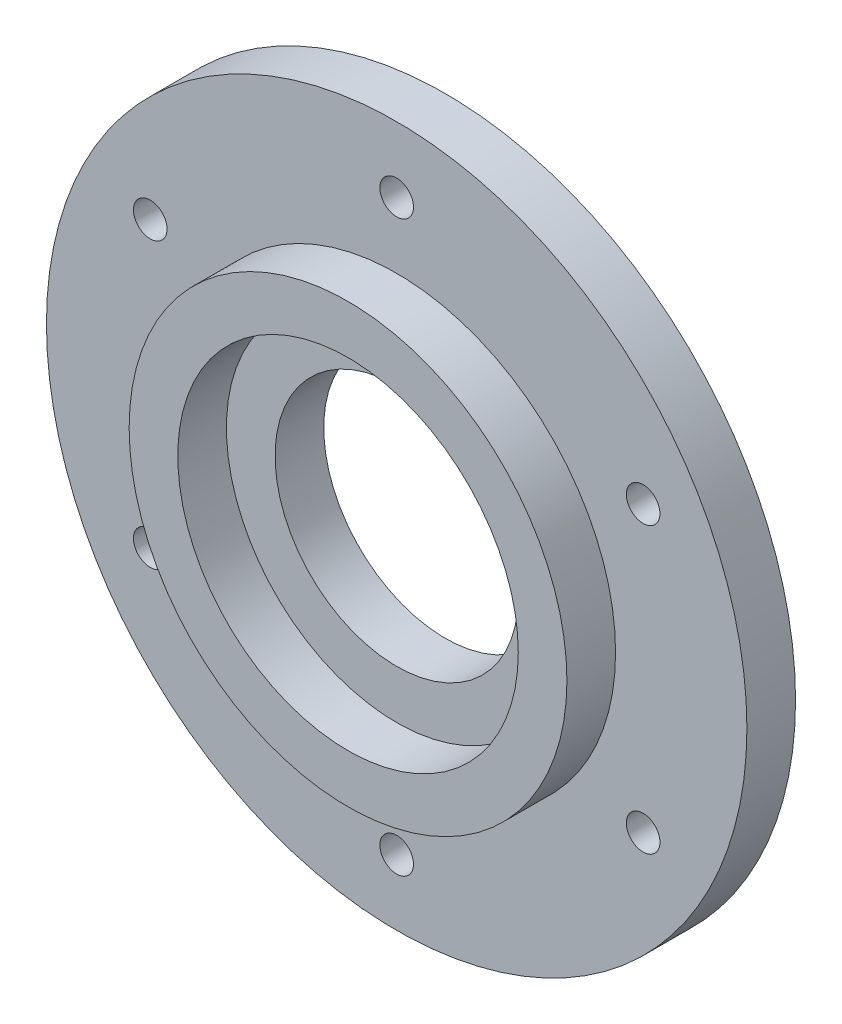
SolidWorks part; units mm, degrees
material "6061-T6 (SS)"
ref_plane "Front Plane" through (0, 0, 0) normal (0, 0, 1) x (1, 0, 0)
ref_plane "Top Plane" through (0, 0, 0) normal (0, 1, 0) x (1, 0, 0)
ref_plane "Right Plane" through (0, 0, 0) normal (1, 0, 0) x (0, 0, -1)
sketch "Sketch Spindle Skeleton" plane through (0, 0, 0) normal (1, 0, 0) x (0, 0, -1)
  line L5 (-1000, 0) -> (49000, 0)
  line L6 (0, -9.5) -> (0, 9.5)
  line L13 (0, 9.5) -> (-48.3, 9.5)
  line L26 (-48.3, 9.5) -> (-48.3, 14)
  line L27 (-48.3, 14) -> (-119.9, 14)
  line L32 (-119.9, 14) -> (-119.9, 9.5)
  line L33 (-119.9, 9.5) -> (-160, 9.5)
  line L34 (-160, 9.5) -> (-160, -9.5)
  line L35 (-160, -9.5) -> (-119.9, -9.5)
  line L36 (-119.9, -9.5) -> (-119.9, -14)
  line L37 (-119.9, -14) -> (-48.3, -14)
  line L38 (-48.3, -14) -> (-48.3, -9.5)
  line L39 (0, -9.5) -> (-48.3, -9.5)
  line L40 (-24.2, 36) -> (-19.2, 36)
  line L41 (-136.5, 22.5) -> (-119.9, 22.5)
  line L42 (-136.5, 22.5) -> (-136.5, -22.5)
  line L43 (-136.5, -22.5) -> (-119.9, -22.5)
  line L44 (-119.9, 22.5) -> (-119.9, -22.5)
  line L45 (-136.5, 22.5) -> (-119.9, -22.5) construction
  line L46 (-136.5, -22.5) -> (-119.9, 22.5) construction
  line L47 (-31.7, 22.5) -> (-48.3, 22.5)
  line L48 (-31.7, 22.5) -> (-31.7, -22.5)
  line L49 (-31.7, -22.5) -> (-48.3, -22.5)
  line L50 (-48.3, 22.5) -> (-48.3, -22.5)
  line L51 (-31.7, 22.5) -> (-48.3, -22.5) construction
  line L52 (-31.7, -22.5) -> (-48.3, 22.5) construction
  line L59 (-19.2, 36) -> (-19.2, -36)
  line L60 (-19.2, -36) -> (-24.2, -36)
  line L61 (-24.2, -22.5) -> (-29.2, -22.5)
  line L62 (-29.2, -22.5) -> (-29.2, -17.5)
  line L63 (-29.2, -17.5) -> (-24.2, -17.5)
  line L64 (-24.2, -17.5) -> (-24.2, 17.5)
  line L65 (-24.2, 17.5) -> (-29.2, 17.5)
  line L66 (-29.2, 17.5) -> (-29.2, 22.5)
  line L67 (-29.2, 22.5) -> (-24.2, 22.5)
  line L68 (-24.2, 22.5) -> (-24.2, 36)
  line L69 (-24.2, -22.5) -> (-24.2, -36)
  line L71 (-141.5, 36) -> (-25.2, 36)
  line L72 (-141.5, 36) -> (-141.5, -36)
  line L73 (-141.5, -36) -> (-25.2, -36)
  line L74 (-25.2, 36) -> (-25.2, -36)
  line L75 (-141.5, 36) -> (-25.2, -36) construction
  line L76 (-141.5, -36) -> (-25.2, 36) construction
  point P3 (0, 0)
  point P18 (-128.2, 0)
  point P24 (-40, 0)
  point P29 (-83.35, 0)
  point P48 (-19.2, 29.25)
revolve "Main Revolve" add sketch "Sketch Spindle Skeleton" angle 360 about L5 region at (0, 20, 27.2) region at (0, 22.65, 21.8091)
sketch "Sketch Center Cut" plane through (0, 0, 24.2) normal (0, 0, 1) x (1, 0, 0)
  circle A0 centre (0, 0) radius 17.5 construction
  circle A1 centre (0, 0) radius 17.5 construction
  circle A2 centre (0, 0) radius 12.5
  dimension "D1" = 5
extrude "Cut Center" cut sketch "Sketch Center Cut" against normal through all
hole_wizard "CBORE for #5 Binding Head Machine Screw1" positions "Hole wizard sketch 1" profile "Hole wizard sketch 2" counterbore size "#5" standard "ANSI Inch" end condition through all
sketch "Hole wizard sketch 1" plane through (0, 0, 19.2) normal (0, 0, -1) x (-1, 0, 0)
  point P0 (0, 29.25)
sketch "Hole wizard sketch 2" plane through (0, 29.25, 19.2) normal (1, 0, 0) x (0, 1, 0)
  line L0 (0, 0) -> (0, 10)
  line L1 (0, 10) -> (1.7272, 10)
  line L3 (1.7272, 10) -> (1.7272, 1.9812)
  line L4 (1.7272, 1.9812) -> (3.7706, 1.9812)
  line L5 (3.7706, 1.9812) -> (3.7706, 0)
  line L7 (3.7706, 0) -> (0, 0)
  line L11 (0, -6.35) -> (0, 107.95) construction
  dimension "Thru Hole Dia." = 3.4544
  dimension "Thru Hole Depth" = 10
  dimension "C'Bore Dia." = 7.5413
  dimension "C'Bore Depth" = 1.9812
pattern_circular "CirPattern1" count 6 over 360 about axis through (0, 0, 19.2) along (0, 0, 1) of "CBORE for #5 Binding Head Machine Screw1"
